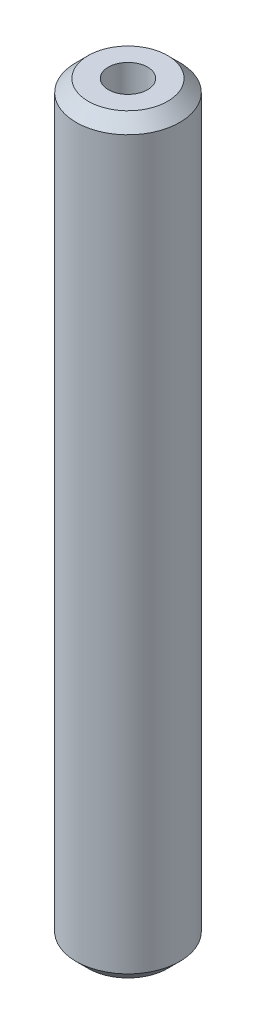
SolidWorks part; units mm, degrees
ref_plane "Front Plane" through (0, 0, 0) normal (0, 0, 1) x (1, 0, 0)
ref_plane "Top Plane" through (0, 0, 0) normal (0, 1, 0) x (1, 0, 0)
ref_plane "Right Plane" through (0, 0, 0) normal (1, 0, 0) x (0, 0, -1)
sketch "Sketch1" plane through (0, 0, 0) normal (0, 1, 0) x (1, 0, 0)
  circle A0 centre (0, 0) radius 7.5
  dimension "SHAFT_OD" = 15
extrude "Boss-Extrude1" add sketch "Sketch1" along normal blind 108.6023
sketch "Sketch2" plane through (0, 0, 0) normal (0, 1, 0) x (1, 0, 0)
  circle A0 centre (0, 0) radius 2.8371
  dimension "BORE_D" = 5.6743
extrude "Cut-Extrude1" cut sketch "Sketch2" along normal through all
chamfer "Chamfer1" distance 1.761 angle 45 2 edges at (0, 108.6023, 7.5) (0, 0, 7.5)
